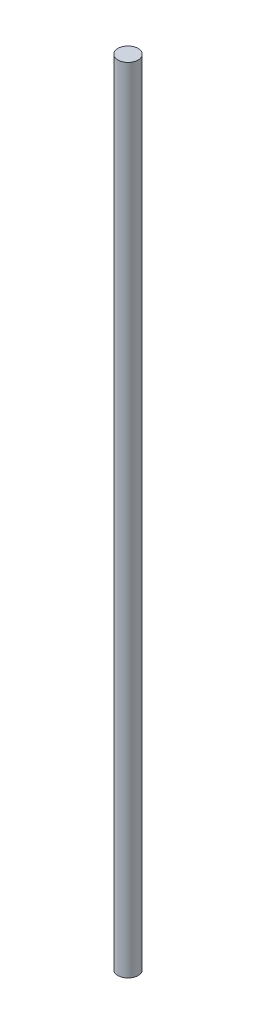
SolidWorks part; units mm, degrees
material "Plain Carbon Steel"
ref_plane "Front Plane" through (0, 0, 0) normal (0, 0, 1) x (1, 0, 0)
ref_plane "Top Plane" through (0, 0, 0) normal (0, 1, 0) x (1, 0, 0)
ref_plane "Right Plane" through (0, 0, 0) normal (1, 0, 0) x (0, 0, -1)
sketch "Sketch1" plane through (0, 0, 0) normal (0, 1, 0) x (1, 0, 0)
  circle A0 centre (0, 0) radius 4.7625
  dimension "D1" = 9.525
extrude "Boss-Extrude1" add sketch "Sketch1" along normal blind 374.65
equation "\"Mid_Coupler_Length\"= 13in"
equation "\"Lead_Screw_Length\" = (\"Mid_Coupler_Length\" + 2*0.375in + 2*0.5in)"
equation "\"D1@Boss-Extrude1\"=\"Lead_Screw_Length\""
